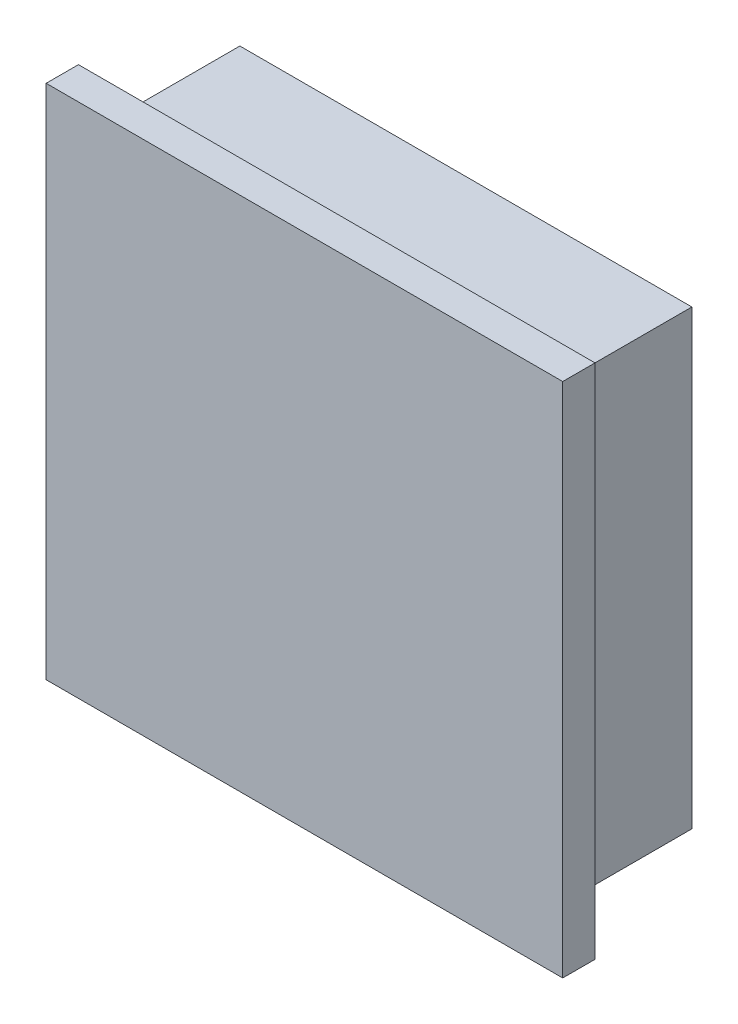
SolidWorks part; units mm, degrees
material "6061-T6 (SS)"
ref_plane "Front Plane" through (0, 0, 0) normal (0, 0, 1) x (1, 0, 0)
ref_plane "Top Plane" through (0, 0, 0) normal (0, 1, 0) x (1, 0, 0)
ref_plane "Right Plane" through (0, 0, 0) normal (1, 0, 0) x (0, 0, -1)
sketch "Sketch1" plane through (0, 0, 0) normal (0, 0, 1) x (1, 0, 0)
  line L1 (0, 0) -> (44.45, 0)
  line L2 (0, 0) -> (0, 44.45)
  line L3 (0, 44.45) -> (44.45, 44.45)
  line L4 (44.45, 0) -> (44.45, 44.45)
  line L5 (-3.175, -3.175) -> (47.625, -3.175)
  line L6 (-3.175, -3.175) -> (-3.175, 47.625)
  line L7 (-3.175, 47.625) -> (47.625, 47.625)
  line L8 (47.625, -3.175) -> (47.625, 47.625)
  dimension "D1" = 44.45
  dimension "D2" = 44.45
  dimension "D3" = 50.8
  dimension "D4" = 50.8
  dimension "D5" = 3.175
  dimension "D6" = 3.175
extrude "Boss-Extrude1" add sketch "Sketch1" along normal blind 3.175 contours L1 L4 L3 L2 | L5 L8 L7 L6 L4 L1 L2 L3 region at (22.225, 22.225, 0) region at (-2.4566, 22.225, 0)
extrude "Boss-Extrude2" add sketch "Sketch1<4>" against normal blind 12.7 contours L1 L4 L3 L2 region at (22.225, 22.225, 0)
sketch "Sketch1<4>" plane through (0, 0, 0) normal (0, 0, 1) x (1, 0, 0) same geometry as "Sketch1"
